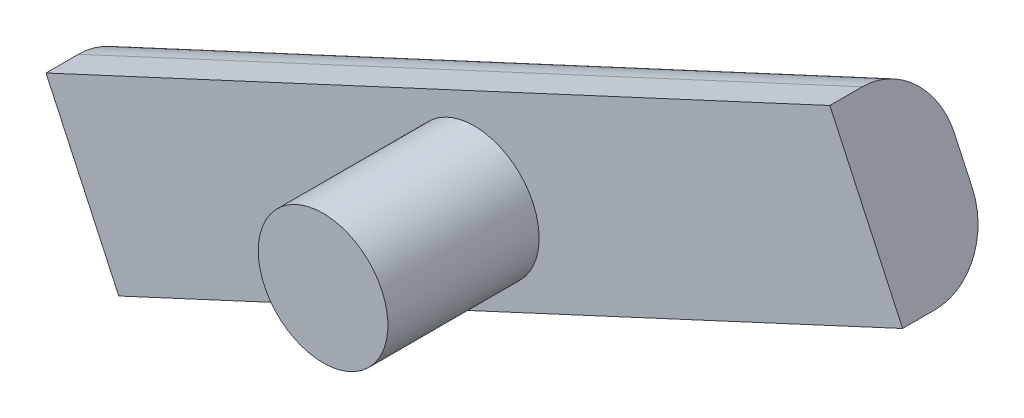
SolidWorks part; units mm, degrees
ref_plane "Alzado" through (0, 0, 0) normal (0, 0, 1) x (1, 0, 0)
ref_plane "Planta" through (0, 0, 0) normal (0, 1, 0) x (1, 0, 0)
ref_plane "Vista lateral" through (0, 0, 0) normal (1, 0, 0) x (0, 0, -1)
sketch3d "Sk_Vastago"
  line L0 (455.3416, 345.3626, 22) -> (455.3416, 345.3626, 15)
sweep "Vastago" add path "Sk_Vastago" circular profile diameter 6 parameters "D3"=6
sketch "Sk_Goma" plane through (0, 0, 0) normal (0, 0, 1) x (1, 0, 0)
  line L0 (438.8839, 333.315) -> (435.5162, 340.5716)
  line L1 (435.5162, 340.5716) -> (471.7992, 357.4103)
  line L2 (471.7992, 357.4103) -> (475.1669, 350.1537)
  line L3 (475.1669, 350.1537) -> (438.8839, 333.315)
extrude "Goma" add sketch "Sk_Goma" along normal blind 4.5 from offset 10.5
fillet "Redondeo2" radius 3 2 edges at (453.6577, 348.9909, 10.5) (457.0254, 341.7343, 10.5)
